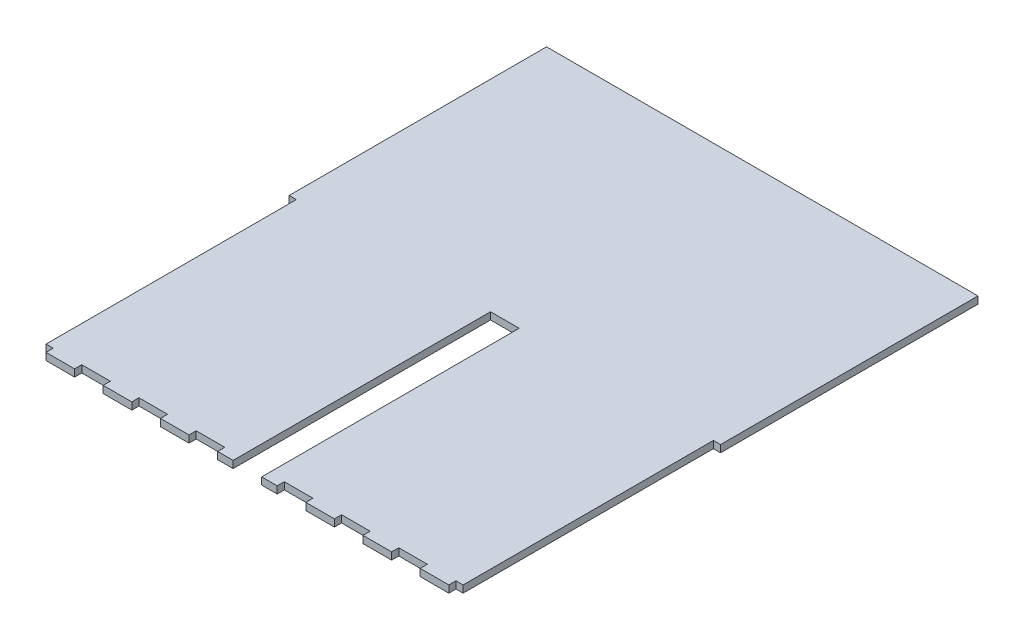
SolidWorks part; units mm, degrees
ref_plane "Front Plane" through (0, 0, 0) normal (0, 0, 1) x (1, 0, 0)
ref_plane "Top Plane" through (0, 0, 0) normal (0, 1, 0) x (1, 0, 0)
ref_plane "Right Plane" through (0, 0, 0) normal (1, 0, 0) x (0, 0, -1)
sketch "Sketch1" plane through (0, 0, 0) normal (0, 1, 0) x (1, 0, 0)
  line L0 (-90.5, 0) -> (-87.5, 0)
  line L2 (-90.5, 0) -> (-90.5, 108)
  line L3 (-90.5, 108) -> (90.5, 108)
  line L4 (90.5, 0) -> (90.5, 108)
  line L5 (-87.5, 0) -> (-87.5, -105)
  line L10 (-84.5, -108) -> (-72.5, -108)
  line L12 (0, 0) -> (0, 108) construction
  line L13 (-87.5, -105) -> (-84.5, -105)
  line L14 (-84.5, -105) -> (-84.5, -108)
  line L15 (-72.5, -108) -> (-72.5, -105)
  line L16 (-72.5, -105) -> (-60.5, -105)
  line L17 (-60.5, -105) -> (-60.5, -108)
  line L18 (-84.5, -105) -> (-72.5, -105) construction
  line L19 (-60.5, -108) -> (-48.5, -108)
  line L20 (-48.5, -108) -> (-48.5, -105)
  line L21 (-48.5, -105) -> (-36.5, -105)
  line L22 (-36.5, -105) -> (-36.5, -108)
  line L23 (-24.5, -108) -> (-24.5, -105)
  line L24 (-24.5, -105) -> (-12.5, -105)
  line L25 (-36.5, -108) -> (-24.5, -108)
  line L26 (-72.5, -108) -> (-48.5, -108) construction
  line L28 (72.5, -108) -> (48.5, -108) construction
  line L29 (84.5, -105) -> (72.5, -105) construction
  line L30 (36.5, -108) -> (24.5, -108)
  line L31 (24.5, -105) -> (12.5, -105)
  line L32 (24.5, -108) -> (24.5, -105)
  line L33 (36.5, -105) -> (36.5, -108)
  line L34 (48.5, -105) -> (36.5, -105)
  line L35 (48.5, -108) -> (48.5, -105)
  line L36 (60.5, -108) -> (48.5, -108)
  line L37 (60.5, -105) -> (60.5, -108)
  line L38 (72.5, -105) -> (60.5, -105)
  line L39 (72.5, -108) -> (72.5, -105)
  line L40 (84.5, -105) -> (84.5, -108)
  line L41 (87.5, -105) -> (84.5, -105)
  line L42 (90.5, 0) -> (87.5, 0)
  line L43 (87.5, 0) -> (87.5, -105)
  line L44 (84.5, -108) -> (72.5, -108)
  line L47 (-6, 0) -> (6, 0)
  line L49 (-12.5, -105) -> (-12.5, -108)
  line L50 (-12.5, -108) -> (-6, -108)
  line L51 (-6, -108) -> (-6, 0)
  line L52 (6, 0) -> (6, -108)
  line L53 (6, -108) -> (12.5, -108)
  line L54 (12.5, -108) -> (12.5, -105)
  line L58 (-12.5, -105) -> (-12.5, -108) [skipped]
  line L59 (-90.5, 0) -> (-90.5, -108) construction
  point P9 (0, 0)
  dimension "D1" = 3
  dimension "D2" = 3
  dimension "D3" = 216
  dimension "D4" = 3
  dimension "D5" = 3
  dimension "D6" = 12
  dimension "D7" = 181
  dimension "D8" = 12
  dimension "D9" = 24
  dimension "D10" = 3
  dimension "D11" = 6.5
extrude "Boss-Extrude1" add sketch "Sketch1" along normal blind 3 contours L24 L49 L50 L51 L47 L52 L53 L54 L31 L32 L30 L33 L34 L35 L36 L37 L38 L39 L44 L40 L41 L43 L42 L4 L3 L2 L0 L5 L13 L14 L10 L15 L16 L17 L19 L20 L21 L22 L25 L23
